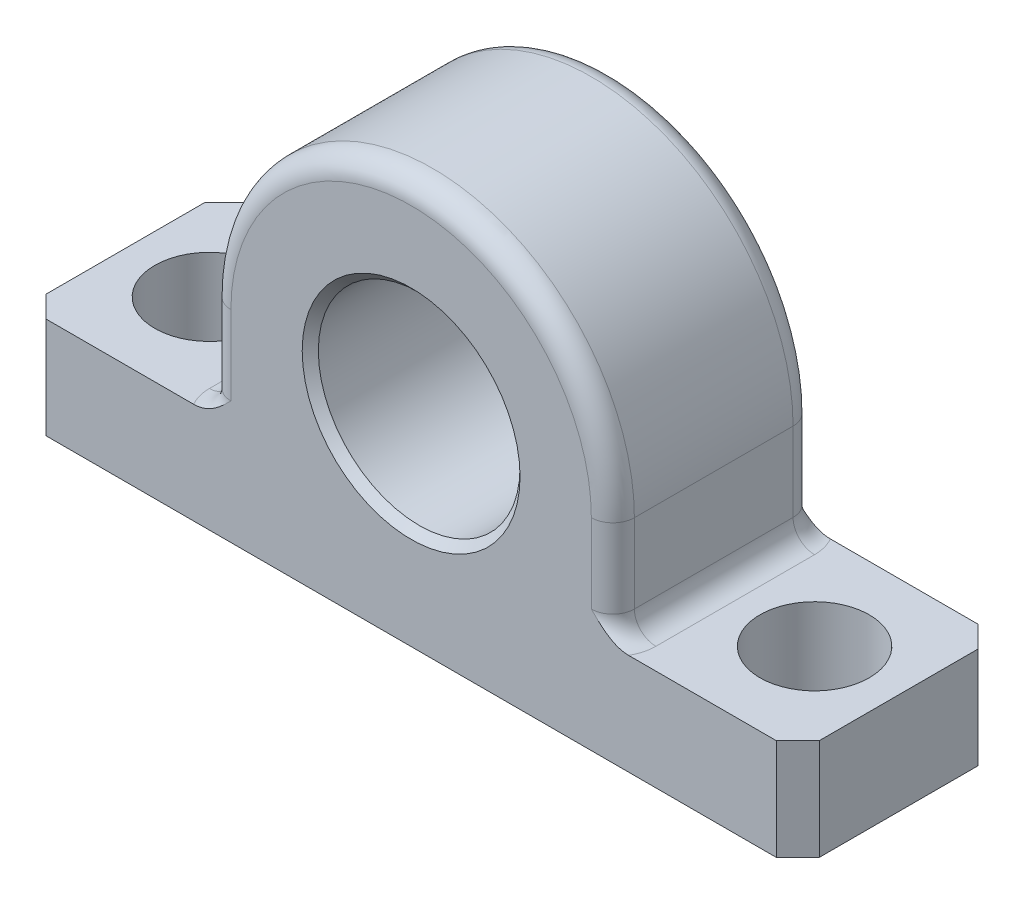
SolidWorks part; units mm, degrees
ref_plane "Front Plane" through (0, 0, 0) normal (0, 0, 1) x (1, 0, 0)
ref_plane "Top Plane" through (0, 0, 0) normal (0, 1, 0) x (1, 0, 0)
ref_plane "Right Plane" through (0, 0, 0) normal (1, 0, 0) x (0, 0, -1)
sketch "Sketch1" plane through (0, 0, 0) normal (0, 0, 1) x (1, 0, 0)
  line L0 (-18.2562, 0) -> (18.2563, 0) construction
  line L1 (18.2563, 0) -> (18.2562, 4.7752) construction
  line L2 (18.2562, 4.7752) -> (9.525, 4.7752) construction
  line L3 (9.525, 4.7752) -> (9.525, 9.525) construction
  line L4 (0, 9.525) -> (0, 0) construction
  line L5 (-18.2562, 0) -> (-18.2562, 4.7752) construction
  line L6 (-18.2562, 4.7752) -> (-9.525, 4.7752) construction
  line L7 (-9.525, 4.7752) -> (-9.525, 9.525) construction
  line L8 (-14.2875, 4.7752) -> (-14.2875, 0) construction
  line L9 (14.2875, 4.7752) -> (14.2875, 0) construction
  circle A0 centre (0, 9.525) radius 4.7625 construction
  arc A1 (9.525, 9.525) -> (-9.525, 9.525) centre (0, 9.525) ccw construction
  point P4 (0, 0)
  point P18 (-16.8672, 4.7752)
  point P19 (-11.7078, 4.7752)
  point P21 (0, 19.05)
  dimension "ID" = 9.525
  dimension "Length (B)" = 36.5125
  dimension "Height (D)" = 19.05
  dimension "Center Height (A)" = 9.525
  dimension "Center to Center (C)" = 28.575
  dimension "Mounting Hole Diameter (F)" = 5.1594
  dimension "Flange Thickness" = 4.7752
sketch "Sketch2" plane through (0, 0, 0) normal (0, 0, 1) x (1, 0, 0)
  line L0 (-18.2562, 0) -> (-18.2562, 4.7752) construction
  line L1 (-18.2562, 0) -> (18.2563, 0) construction
  line L2 (18.2563, 0) -> (18.2562, 4.7752) construction
  line L3 (18.2562, 4.7752) -> (9.525, 4.7752) construction
  line L4 (9.525, 4.7752) -> (9.525, 9.525) construction
  line L5 (-9.525, 4.7752) -> (-9.525, 9.525) construction
  line L6 (-18.2562, 4.7752) -> (-9.525, 4.7752) construction
  line L7 (-18.2562, 0) -> (-18.2562, 4.7752)
  line L8 (-18.2562, 0) -> (18.2563, 0)
  line L9 (18.2563, 0) -> (18.2562, 4.7752)
  line L10 (18.2562, 4.7752) -> (9.525, 4.7752)
  line L11 (9.525, 4.7752) -> (9.525, 9.525)
  line L12 (-9.525, 4.7752) -> (-9.525, 9.525)
  line L13 (-18.2562, 4.7752) -> (-9.525, 4.7752)
  arc A0 (9.525, 9.525) -> (-9.525, 9.525) centre (0, 9.525) ccw construction
  arc A1 (9.525, 9.525) -> (-9.525, 9.525) centre (0, 9.525) ccw
  circle A2 centre (0, 9.525) radius 4.7625 construction
  circle A3 centre (0, 9.525) radius 4.7625
extrude "Body Extrude" add sketch "Sketch2" along normal mid plane 9.525
fillet "Body Fillet A" radius 1.016 6 edges at (9.525, 7.1501, 4.7625) (0, 19.05, 4.7625) (-9.525, 7.1501, 4.7625) (-9.525, 7.1501, -4.7625) (0, 19.05, -4.7625) (9.525, 7.1501, -4.7625)
fillet "Body Fillet B" radius 1.016 6 edges at (9.2274, 4.7752, 4.4649) (9.2274, 4.7752, -4.4649) (-9.2274, 4.7752, 4.4649) (-9.2274, 4.7752, -4.4649) (9.525, 4.7752, 0) (-9.525, 4.7752, 0)
chamfer "Chamfer2" distance 1.016 angle 45 4 edges at (18.2562, 2.3876, -4.7625) (18.2562, 2.3876, 4.7625) (-18.2562, 2.3876, -4.7625) (-18.2562, 2.3876, 4.7625)
chamfer "ID Chamfer" distance 0.381 angle 45 2 edges at (4.7625, 9.525, -4.7625) (4.7625, 9.525, 4.7625)
sketch "Sketch3" plane through (0, 4.7752, 0) normal (0, 1, 0) x (1, 0, 0)
  line L0 (-18.2562, 0) -> (-9.525, 0) construction
  line L1 (0, 0) -> (0, 4.7625) construction
  line L2 (4.7625, 4.7625) -> (-4.7625, 4.7625) construction
  circle A0 centre (-14.2875, 0) radius 2.5797
  circle A1 centre (14.2875, 0) radius 2.5797
extrude "Hole Cut" cut sketch "Sketch3" against normal through all
ref_axis "Center Axis 1" through (0, 9.525, 4.3815) along (0, 0, -1)
ref_axis "Center Axis 2" through (-14.2875, 0, 0) along (0, 1, 0)
ref_axis "Center Axis 3" through (14.2875, 0, 0) along (0, 1, 0)
ref_plane "Contact Plane 1" through (0, 0, 0) normal (0, -1, 0) x (-1, 0, 0)
equation "\"D1@Body Fillet B\" = \"Radius@Body Fillet A\""
equation "\"D1@Chamfer2\"=\"Radius@Body Fillet A\""
